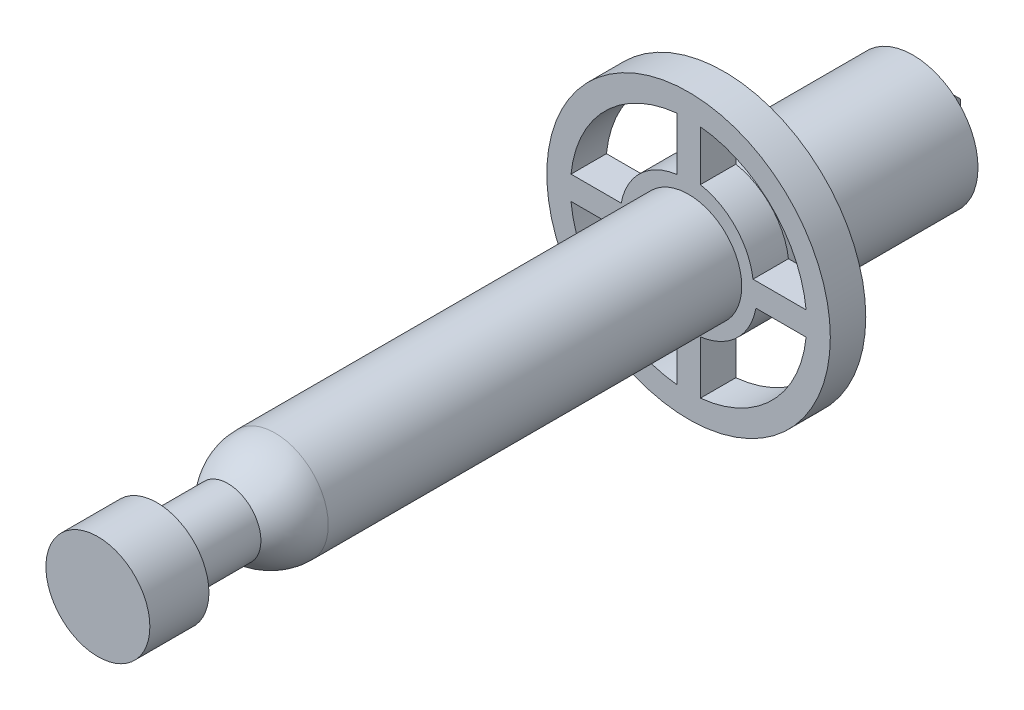
SolidWorks part; units mm, degrees
ref_plane "Front Plane" through (0, 0, 0) normal (0, 0, 1) x (1, 0, 0)
ref_plane "Top Plane" through (0, 0, 0) normal (0, 1, 0) x (1, 0, 0)
ref_plane "Right Plane" through (0, 0, 0) normal (1, 0, 0) x (0, 0, -1)
sketch "Sketch1" plane through (0, 0, 0) normal (0, 0, 1) x (1, 0, 0)
  circle A0 centre (0, -0.1473) radius 2.75
  dimension "D1" = 5.5
extrude "Boss-Extrude1" add sketch "Sketch1" along normal blind 8
sketch "Sketch4" plane through (0, 0, 0) normal (0, 1, 0) x (1, 0, 0)
  line L0 (0, 0) -> (0, 2)
  line L1 (0, 2) -> (-2, 0)
  line L2 (2.75, 0) -> (-2.75, 0) construction
  line L3 (-2, 0) -> (0, 0)
  dimension "D1" = 2
revolve "Revolve2" add sketch "Sketch4" angle 360 about L0
sketch "Sketch5" plane through (0, 0, 8) normal (0, 0, 1) x (1, 0, 0)
  circle A0 centre (0, 0) radius 2.25
  dimension "D1" = 4.5
extrude "Boss-Extrude2" add sketch "Sketch5" along normal blind 19
sketch "Sketch6" plane through (0, 0, 8) normal (0, 0, 1) x (1, 0, 0)
  circle A0 centre (0, 0) radius 6
  dimension "D1" = 12
extrude "Boss-Extrude4" add sketch "Sketch6" along normal blind 1.5
sketch "Sketch7" plane through (0, 0, 8) normal (0, 0, -1) x (-1, 0, 0)
  line L0 (0, 5) -> (0, 2.6027) construction
  line L1 (-5, 0) -> (-2.7461, 0) construction
  line L2 (-0.5, 4.9749) -> (-0.5, 2.5568)
  line L3 (0.5, 4.9749) -> (0.5, 2.5568)
  line L4 (-0.5, -2.8515) -> (-0.5, -4.9749)
  line L5 (0, -2.8973) -> (0, -5) construction
  line L6 (0.5, -2.8515) -> (0.5, -4.9749)
  line L7 (2.7461, 0) -> (5, 0) construction
  line L8 (-4.9749, -0.5) -> (-2.7273, -0.5)
  line L9 (-4.9749, 0.5) -> (-2.6727, 0.5)
  line L10 (2.7273, -0.5) -> (4.9749, -0.5)
  line L11 (2.6727, 0.5) -> (4.9749, 0.5)
  circle A0 centre (0, 0) radius 5
  circle A1 centre (0, 0) radius 6 construction
  circle A2 centre (0, -0.1473) radius 2.75 construction
  circle A3 centre (0, -0.1473) radius 2.75
  circle M9 centre (0, -0.1473) radius 2.75
  dimension "D1" = 1
  dimension "D2" = 0.5
  dimension "D3" = 0.5
extrude "Cut-Extrude1" cut sketch "Sketch7" against normal blind 1.5 contours L6 A0 L10 M9 region at (-2.6609, -2.6455, 8)
pattern_circular "CirPattern1" count 4 over 360 about axis through (0, 0, 8) along (0, 0, 1) of "Cut-Extrude1"
sketch "Sketch10" plane through (0, 0, 0) normal (1, 0, 0) x (0, 0, -1)
  line L0 (-27, 0) -> (-29, 0)
  line L1 (-27, 2.25) -> (-27, -2.25) construction
  line L2 (-29, 0) -> (-29, 1.4)
  line L3 (-27, 0) -> (-27, 2.25)
  line L4 (-9.5, 2.25) -> (-27, 2.25) construction
  spline S0 degree 2 poles (-29, 1.4) (-28.0866, 2.25) (-27, 2.25) knots 0 0 0 1 1 1
  dimension "D1" = 2
  dimension "D2" = 1.4
  dimension "D3" = 2.25
revolve "Revolve3" add sketch "Sketch10" angle 360 about L0
sketch "Sketch11" plane through (0, 0, 29) normal (0, 0, 1) x (1, 0, 0)
  circle A0 centre (0, 0) radius 1.4 construction
  circle A1 centre (0, 0) radius 1.4
extrude "Boss-Extrude5" add sketch "Sketch11" along normal blind 3
sketch "Sketch12" plane through (0, 0, 32) normal (0, 0, 1) x (1, 0, 0)
  circle A0 centre (0, 0) radius 2.2
  dimension "D1" = 4.4
extrude "Boss-Extrude6" add sketch "Sketch12" along normal blind 2.5
